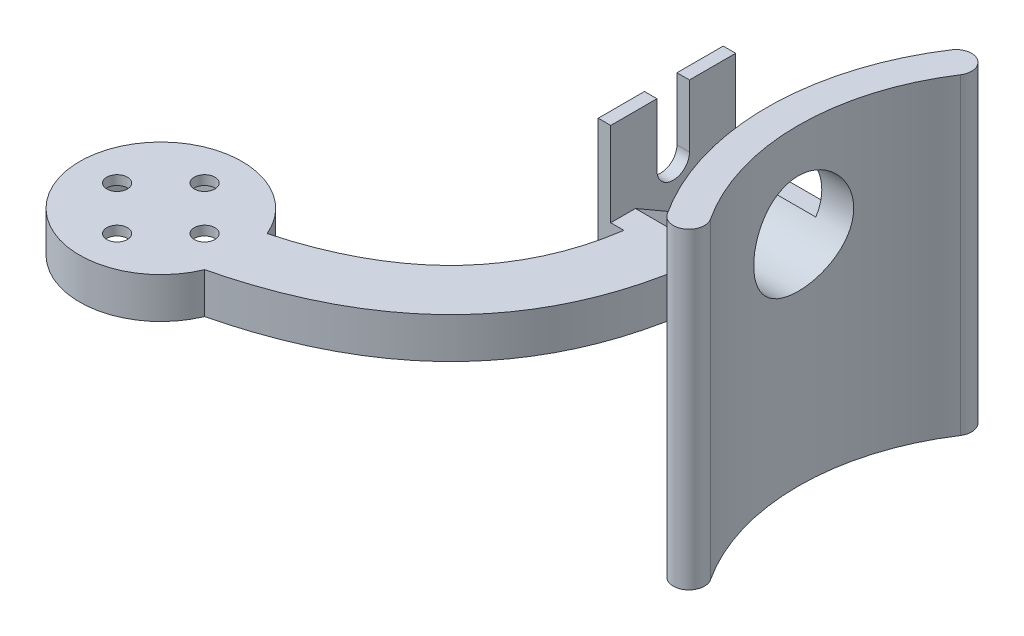
SolidWorks part; units mm, degrees
ref_plane "Plan de face" through (0, 0, 0) normal (0, 0, 1) x (1, 0, 0)
ref_plane "Plan de dessus" through (0, 0, 0) normal (0, 1, 0) x (1, 0, 0)
ref_plane "Plan de droite" through (0, 0, 0) normal (1, 0, 0) x (0, 0, -1)
sketch "Esquisse1" plane through (0, 0, 0) normal (0, 1, 0) x (1, 0, 0)
  line L0 (-30.5328, 20) -> (-30.5328, -20) construction
  line L1 (-30.5328, 0) -> (0, 0) construction
  circle A0 centre (0, 0) radius 36.5 construction
  arc A2 (-32.6241, -21.3699) -> (-32.6241, 21.3699) centre (0, 0) cw construction
  arc A3 (-34.7153, 22.7397) -> (-34.7153, -22.7397) centre (0, 0) ccw
  arc A4 (-30.5328, 20) -> (-30.5328, -20) centre (0, 0) ccw
  arc A5 (-30.5328, 20) -> (-34.7153, 22.7397) centre (-32.6241, 21.3699) ccw
  arc A6 (-34.7153, -22.7397) -> (-30.5328, -20) centre (-32.6241, -21.3699) ccw
  point P9 (-39, 0)
  dimension "D1" = 73
  dimension "D3" = 2.5
  dimension "D2" = 40
extrude "Boss.-Extru.1" add sketch "Esquisse1" along normal blind 50
sketch "Esquisse2" plane through (0, 0, 0) normal (1, 0, 0) x (0, 0, -1)
  line L0 (0, 35) -> (0, 0) construction
  circle A0 centre (0, 35) radius 8
  dimension "D1" = 16
  dimension "D2" = 35
extrude "Enlèv. mat.-Extru.1" cut sketch "Esquisse2" against normal through all
ref_plane "Plan1" through (-41.5, 0, 0) normal (-1, 0, 0) x (0, 0, 1)
ref_plane "Plan2" through (-56.5, 0, 0) normal (-1, 0, 0) x (0, 0, 1)
sketch "Esquisse4" plane through (-56.5, 0, 0) normal (-1, 0, 0) x (0, 0, 1)
  line L0 (-2.6, 35) -> (-2.6, 45)
  line L1 (-10, 25) -> (10, 25)
  line L2 (-10, 25) -> (-10, 45)
  line L3 (-10, 45) -> (10, 45) construction
  line L4 (10, 25) -> (10, 45)
  line L5 (-10, 25) -> (10, 45) construction
  line L6 (-10, 45) -> (10, 25) construction
  line L7 (2.6, 35) -> (2.6, 45)
  line L8 (-10, 45) -> (-2.6, 45)
  line L9 (2.6, 45) -> (10, 45)
  circle A0 centre (0, 35) radius 2.6 construction
  arc A1 (-2.6, 35) -> (2.6, 35) centre (0, 35) ccw
  dimension "D1" = 5.2
  dimension "D2" = 20
extrude "Boss.-Extru.3" add sketch "Esquisse4" along normal blind 2 separate body
sketch "Esquisse6" plane through (-56.5, 0, 0) normal (-1, 0, 0) x (0, 0, 1)
  line L0 (-6.05, 31.507) -> (-6.05, 38.493) construction
  line L1 (-6.05, 38.493) -> (0, 41.9859) construction
  line L2 (0, 41.9859) -> (6.05, 38.493) construction
  line L3 (6.05, 38.493) -> (6.05, 31.507) construction
  line L4 (6.05, 31.507) -> (0, 28.0141)
  line L5 (0, 28.0141) -> (-6.05, 31.507)
  line L6 (-6.05, 38.493) -> (6.05, 38.493) construction
  line L7 (-6.05, 38.493) -> (6.05, 31.507) construction
  line L8 (-6.05, 31.507) -> (-10, 31.507)
  line L9 (-10, 45) -> (-10, 25) construction
  line L10 (-10, 31.507) -> (-10, 25)
  line L11 (-10, 25) -> (10, 25)
  line L12 (10, 25) -> (10, 31.507)
  line L13 (10, 25) -> (10, 45) construction
  line L14 (10, 31.507) -> (6.05, 31.507)
  line L15 (-10, 25) -> (10, 25) construction
  point P4 (0, 35)
  point P7 (0, 35)
  dimension "D1" = 12.1
  dimension "D2" = 120
extrude "Boss.-Extru.4" add sketch "Esquisse6" against normal blind 8
sketch "Esquisse7" plane through (-48.5, 0, 0) normal (1, 0, 0) x (0, 0, -1)
  line L0 (-7.1972, 31.507) -> (7.1972, 31.507) construction
  line L2 (6.05, 31.507) -> (10, 31.507) construction
  line L3 (7.1972, 31.507) -> (10, 31.507)
  line L4 (10, 31.507) -> (10, 25)
  line L5 (10, 25) -> (-10, 25)
  line L6 (-10, 25) -> (-10, 31.507)
  line L7 (-10, 31.507) -> (-7.1972, 31.507)
  line L9 (10, 25) -> (-10, 25) construction
  circle A0 centre (0, 35) radius 8 construction
  arc A1 (-7.1972, 31.507) -> (7.1972, 31.507) centre (0, 35) ccw
  dimension "D1" = 16
  dimension "D2" = 20
extrude "Boss.-Extru.5" add sketch "Esquisse7" along normal up to surface (7.6289 mm away) up to face at (-41.4662, 42.8228, 1.6746)
sketch "Esquisse8" plane through (0, 25, 0) normal (0, -1, 0) x (1, 0, 0)
  line L0 (-58.5, 0) -> (-94.5001, 0) construction
  line L2 (-94.5001, 0) -> (-94.5001, 44) construction
  line L4 (-58.0357, 21.4645) -> (-50.9646, 28.5355) construction
  line L6 (-54.5001, 25) -> (-54.5001, 0) construction
  line L7 (-54.5001, 25) -> (-94.5001, 25) construction
  line L8 (-82.5001, 39) -> (-82.5001, 49) construction
  line L9 (-94.5001, 44) -> (-87.5001, 44) construction
  line L10 (-58.5, -10) -> (-58.5, 10) construction
  line L11 (-40.2772, 10) -> (-58.5, 10) construction
  line L12 (-54.3886, 10) -> (-44.3886, 10)
  line L13 (-87.5001, 44) -> (-82.5001, 44) construction
  circle A0 centre (-94.5001, 44) radius 13 construction
  arc A1 (-82.5001, 49) -> (-82.5001, 39) centre (-94.5001, 44) ccw
  circle A2 centre (-87.5001, 44) radius 1.65
  circle A3 centre (-94.5001, 37) radius 1.65
  circle A4 centre (-101.5001, 44) radius 1.65
  circle A5 centre (-94.5001, 51) radius 1.65
  spline S0 degree 2 poles (-82.5001, 39) (-57.709, 32.3018) (-54.3886, 10) knots 0 0 0 1 1 1
  spline S3 degree 2 poles (-82.5001, 49) (-49.0005, 40.8974) (-44.3886, 10) knots 0 0 0 1 1 1
  point P10 (-49.3886, 10)
  point P11 (-94.5001, 44)
  point P30 (-94.5001, 44)
  point P43 (-49.3886, 10)
  dimension "D4" = 26
  dimension "D8" = 3.3
  dimension "D1" = 36.0001
  dimension "D2" = 44
  dimension "D3" = 10
  dimension "D5" = 40
  dimension "D6" = 25
  dimension "D7" = 45
  dimension "D9" = 7
  dimension "D10" = 4
extrude "Boss.-Extru.6" add sketch "Esquisse8" against normal up to surface (6.507 mm away) up to face at (-48.5288, 31.507, 7.7499)
sketch "Esquisse9" plane through (0, 25, 0) normal (0, -1, 0) x (1, 0, 0)
  circle A0 centre (-94.5001, 44) radius 10.5
  dimension "D1" = 21
extrude "Enlèv. mat.-Extru.2" cut sketch "Esquisse9" against normal offset from surface (5.007 mm away) 1.5 up to face at (-58.495, 31.507, 15.9499)
